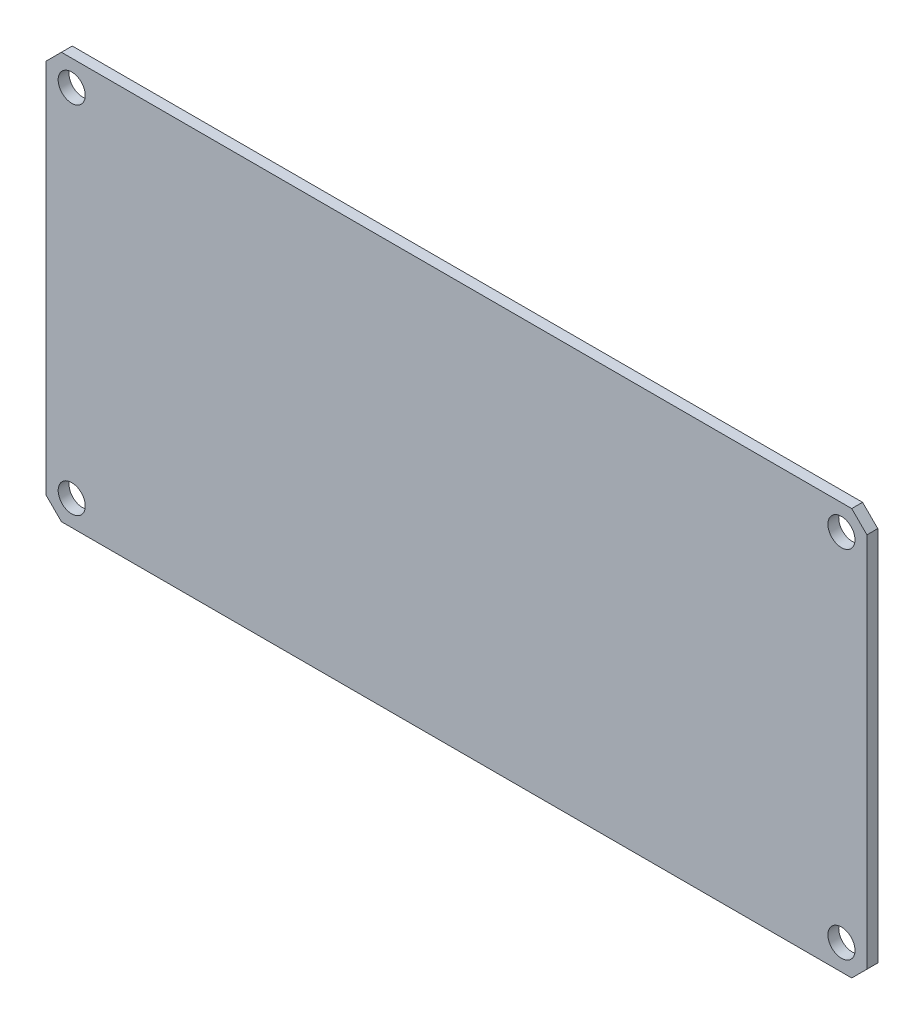
SolidWorks part; units mm, degrees
ref_plane "Front Plane" through (0, 0, 0) normal (0, 0, 1) x (1, 0, 0)
ref_plane "Top Plane" through (0, 0, 0) normal (0, 1, 0) x (1, 0, 0)
ref_plane "Right Plane" through (0, 0, 0) normal (1, 0, 0) x (0, 0, -1)
sketch "Sketch1" plane through (0, 0, 0) normal (0, 0, 1) x (1, 0, 0)
  line L1 (0, -18.75) -> (-33.8, -18.75)
  line L2 (0, -18.75) -> (0, 18.75)
  line L3 (0, 18.75) -> (-33.8, 18.75)
  line L4 (-33.8, -18.75) -> (-33.8, 18.75)
  line L5 (-31.8, -4.9) -> (-31.8, -14.1) construction
  dimension "D1" = 37.5
  dimension "D2" = 2
extrude "Boss-Extrude-NoAnt" add sketch "Sketch1" along normal blind 1
sketch "Sketch2" plane through (0, 0, 0) normal (0, 0, 1) x (1, 0, 0)
  line L1 (0, 18.75) -> (41.9, 18.75)
  line L2 (0, 18.75) -> (0, -18.75)
  line L3 (0, -18.75) -> (41.9, -18.75)
  line L4 (41.9, 18.75) -> (41.9, -18.75)
  line L5 (-33.8, -18.75) -> (0, -18.75) construction
  dimension "D1" = 41.9
extrude "Boss-Extrude-Ant" add sketch "Sketch2" along normal up to surface (1 mm away) up to face at (-16.9, 0, 1)
sketch "Sketch3" plane through (0, 0, 0) normal (0, 0, -1) x (-1, 0, 0)
  line L0 (31.45, -16.4) -> (-39.55, -16.4) construction
  line L1 (-39.55, -16.4) -> (-39.55, 16.4) construction
  line L2 (-39.55, 16.4) -> (31.45, 16.4) construction
  line L3 (31.45, 16.4) -> (31.45, -16.4) construction
  line L4 (-41.9, 18.75) -> (33.8, 18.75) construction
  line L5 (31.45, 16.4) -> (31.45, 18.75) construction
  line L6 (31.45, 16.4) -> (33.8, 16.4) construction
  line L7 (33.8, 18.75) -> (33.8, -18.75) construction
  line L8 (-39.55, 16.4) -> (-41.9, 16.4) construction
  line L9 (-41.9, -18.75) -> (-41.9, 18.75) construction
  line L10 (31.45, -16.4) -> (31.45, -18.75) construction
  line L11 (33.8, -18.75) -> (-41.9, -18.75) construction
  circle A0 centre (31.45, -16.4) radius 1.25
  circle A1 centre (-39.55, -16.4) radius 1.25
  circle A2 centre (-39.55, 16.4) radius 1.25
  circle A3 centre (31.45, 16.4) radius 1.25
  dimension "D1" = 2.5
  dimension "D2" = 2.35
extrude "Holes" cut sketch "Sketch3" against normal through all
sketch "Sketch4" plane through (0, 0, 0) normal (0, 0, -1) x (-1, 0, 0)
  line L0 (-41.9, 18.75) -> (-40.5, 18.75)
  line L1 (-41.9, 18.75) -> (33.8, 18.75) construction
  line L2 (-40.5, 18.75) -> (-41.9, 17.35)
  line L3 (-41.9, -18.75) -> (-41.9, 18.75) construction
  line L4 (-41.9, 17.35) -> (-41.9, 18.75)
  line L5 (-41.4626, 16.2552) -> (-39.3888, 18.3289) construction
  line L6 (-4.05, 18.75) -> (-4.05, -18.75) construction
  line L7 (33.8, -18.75) -> (-41.9, -18.75) construction
  line L8 (-41.9, 0) -> (33.8, 0) construction
  line L9 (33.8, 18.75) -> (33.8, -18.75) construction
  line L10 (-41.9, -17.35) -> (-41.9, -18.75)
  line L11 (-40.5, -18.75) -> (-41.9, -17.35)
  line L12 (-41.9, -18.75) -> (-40.5, -18.75)
  line L13 (33.8, -18.75) -> (32.4, -18.75)
  line L14 (32.4, -18.75) -> (33.8, -17.35)
  line L15 (33.8, -17.35) -> (33.8, -18.75)
  line L16 (33.8, 17.35) -> (33.8, 18.75)
  line L17 (32.4, 18.75) -> (33.8, 17.35)
  line L18 (33.8, 18.75) -> (32.4, 18.75)
  circle A0 centre (-39.55, 16.4) radius 1.25 construction
  dimension "D1" = 1.4
  dimension "D2" = 1.0835
extrude "Corners" cut sketch "Sketch4" against normal through all
